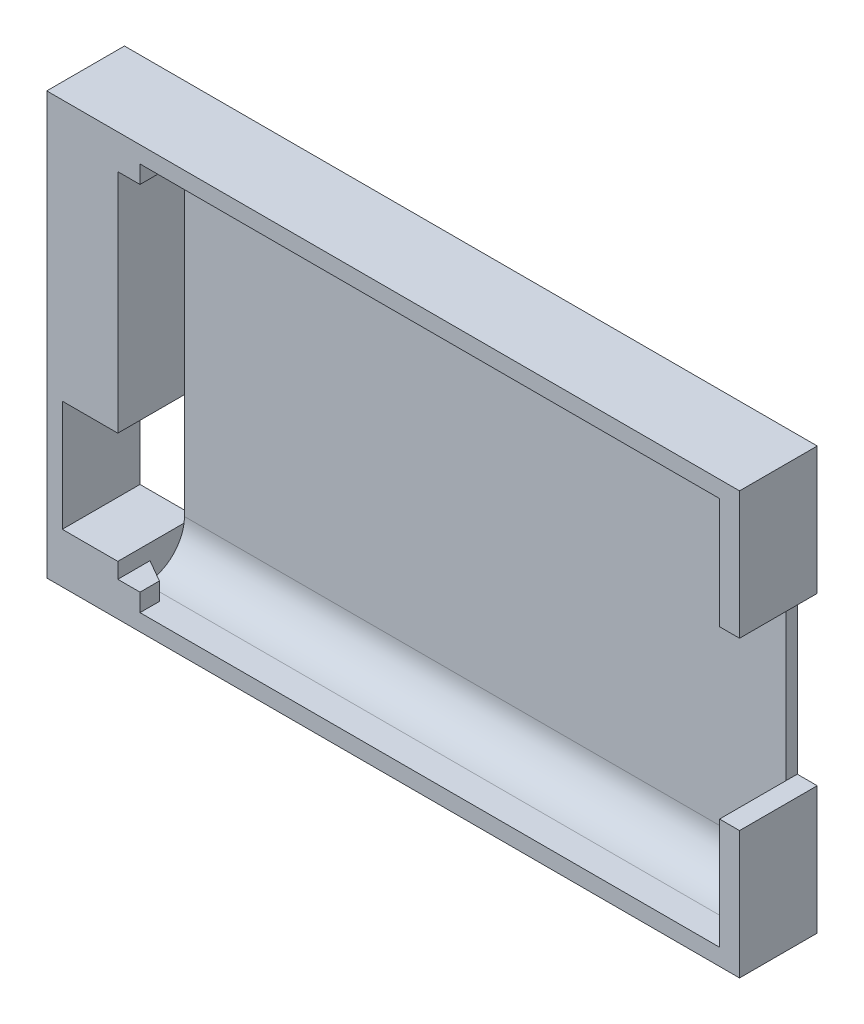
SolidWorks part; units mm, degrees
ref_plane "Front Plane" through (0, 0, 0) normal (0, 0, 1) x (1, 0, 0)
ref_plane "Top Plane" through (0, 0, 0) normal (0, 1, 0) x (1, 0, 0)
ref_plane "Right Plane" through (0, 0, 0) normal (1, 0, 0) x (0, 0, -1)
sketch "Sketch1" plane through (0, 0, 0) normal (0, 0, 1) x (1, 0, 0)
  line L1 (-26.5, 17) -> (26.5, 17)
  line L2 (-26.5, 17) -> (-26.5, -17)
  line L3 (-26.5, -17) -> (26.5, -17)
  line L4 (26.5, 17) -> (26.5, -17)
  line L5 (-26.5, 17) -> (26.5, -17) construction
  line L6 (-26.5, -17) -> (26.5, 17) construction
  point P0 (0, 0)
  dimension "D1" = 34
  dimension "D2" = 53
sketch "Sketch2" plane through (0, 0, 0) normal (0, 0, 1) x (1, 0, 0)
  line L1 (-33.5, 19) -> (28.9, 19)
  line L2 (-33.5, 19) -> (-33.5, -19)
  line L3 (-33.5, -19) -> (28.9, -19)
  line L4 (28.9, 19) -> (28.9, -19)
  line L6 (-26.5, 17) -> (-26.5, -17) construction
  line L7 (26.5, 17) -> (26.5, -17) construction
  line L8 (-26.5, -17) -> (-26.5, -19) construction
  line L9 (-26.5, 17) -> (-26.5, 19) construction
  line L10 (-26.5, 17) -> (26.5, 17) construction
  dimension "D1" = 7
  dimension "D2" = 2.4
  dimension "D3" = 2
extrude "Boss-Extrude1" add sketch "Sketch2" along normal blind 7
sketch "Sketch3" plane through (0, 0, 0) normal (1, 0, 0) x (0, 0, -1)
  line L0 (-7.5, 17) -> (-4.5, 17) construction
  line L1 (-1.5, 0) -> (-7.5, 0) construction
  line L2 (-7.5, -17) -> (-7.5, 17) construction
  line L3 (-1.5, -14) -> (-1.5, 14) construction
  line L4 (-7.5, -17) -> (-4.5, -17) construction
  line L5 (-8, 17.5) -> (-4.5, 17.5)
  line L6 (-1, -14) -> (-1, 14)
  line L7 (-8, -17.5) -> (-4.5, -17.5)
  line L8 (-8, -17.5) -> (-8, 17.5)
  arc A0 (-4.5, 17) -> (-1.5, 14) centre (-4.5, 14) cw construction
  arc A1 (-4.5, -17) -> (-1.5, -14) centre (-4.5, -14) ccw construction
  arc A2 (-4.5, 17.5) -> (-1, 14) centre (-4.5, 14) cw
  arc A3 (-4.5, -17.5) -> (-1, -14) centre (-4.5, -14) ccw
  point P6 (-12.641, 14.088)
  point P11 (-13.7836, 13.0913)
  dimension "D1" = 3
  dimension "D2" = 6
  dimension "D3" = 34
  dimension "D5" = 1
  dimension "D4" = 0.5
extrude "Cut-Extrude1" cut sketch "Sketch3" against normal mid plane 54.2
sketch "Sketch4" plane through (0, 0, 7) normal (0, 0, 1) x (1, 0, 0)
  line L1 (0, 0) -> (28, 0) construction
  line L2 (28.9, 7.5) -> (27.1, 7.5)
  line L3 (28.9, 7.5) -> (28.9, -7.5)
  line L4 (28.9, -7.5) -> (27.1, -7.5)
  line L7 (27.1, 7.5) -> (27.1, -7.5)
  line L8 (28.9, 7.5) -> (27.1, -7.5) construction
  line L9 (28.9, -7.5) -> (27.1, 7.5) construction
  line L10 (27.1, -14) -> (27.1, 14) construction
  line L11 (28.9, -19) -> (28.9, 19) construction
  line L12 (27.1, 17.5) -> (27.1, -17.5) construction
  point P0 (28, 0)
  point P12 (27.1, -5.5675)
  dimension "D1" = 15
extrude "ForFinger" cut sketch "Sketch4" against normal through all
sketch "Sketch8" plane through (0, 0, 1) normal (0, 0, 1) x (1, 0, 0)
  line L0 (-27.1, -17.5) -> (27.1, -17.5) construction
  line L1 (-27.1, 17.5) -> (-24.1, 17.5)
  line L2 (-27.1, 17.5) -> (-27.1, -17.5)
  line L3 (-27.1, -17.5) -> (-24.1, -17.5)
  line L4 (-24.1, 17.5) -> (-24.1, -17.5)
  dimension "D1" = 3
extrude "Cut-Extrude4" [suppressed] cut sketch "Sketch8" along normal through all
sketch "Sketch5" plane through (0, 17.5, 0) normal (0, -1, 0) x (1, 0, 0)
  line L0 (-27.1, 7) -> (-25.1, 7)
  line L1 (27.1, 7) -> (-27.1, 7) construction
  line L2 (-25.1, 7) -> (-25.1, 4.1)
  line L3 (-25.1, 4.1) -> (-27.1, 4.1)
  line L4 (-27.1, 4.1) -> (-27.1, 7)
  line L5 (-26.9, 4) -> (-24.9, 4) construction
  line L6 (-24.9, 4) -> (-24.9, 7) construction
  line L7 (-24.9, 7) -> (-20.5432, 7) construction
  line L8 (-26.9, 4) -> (-26.9, 1) construction
  line L9 (-26.9, 1) -> (-20.5432, 1) construction
  line L10 (-20.5432, 1) -> (-20.5432, 7) construction
  line L11 (-27.1, 1) -> (27.1, 1) construction
  line L12 (-27.1, 1) -> (-27.1, 4.5) construction
  point P9 (0, 0)
  point P14 (0, 0)
  point P15 (-20.5432, 1)
  point P18 (-24.4325, 2.1847)
  point P19 (-24.0137, 1)
  point P20 (-26.3689, 1)
  point P23 (-27.1, 3.7068)
  point P24 (-25.203, 5.2626)
  point P25 (-27.1, 4.2847)
  point P26 (-25.0697, 4.2847)
  dimension "D1" = 6
  dimension "D2" = 3
  dimension "D3" = 0.2
  dimension "D4" = 2
  dimension "D5" = 0.2
  dimension "D6" = 0.1
extrude "Boss-Extrude2" add sketch "Sketch5" along normal blind 1.6
chamfer "Chamfer1" distance 2 angle 30 1 edges at (-25.1, 16.6885, 4.1) first distance on face at (-26.1, 16.6885, 4.1)
mirror "Mirror1" about plane through (0, 0, 0) normal (0, 1, 0) of "Chamfer1", "Boss-Extrude2"
sketch "Sketch6" plane through (0, 0, 7) normal (0, 0, 1) x (1, 0, 0)
  line L1 (-32.1, -4.5) -> (-27.1, -4.5)
  line L2 (-32.1, -4.5) -> (-32.1, -14.5)
  line L3 (-32.1, -14.5) -> (-27.1, -14.5)
  line L4 (-27.1, -4.5) -> (-27.1, -14.5)
  line L5 (-27.1, -15.9) -> (-27.1, 15.9) construction
  line L7 (-26.5, -17) -> (26.5, -17) construction
  point P4 (-30.9225, -14.5)
  point P8 (-32.1, -9.5)
  dimension "D1" = 10
  dimension "D2" = 7.5
  dimension "D3" = 5
extrude "Cut-Extrude3" cut sketch "Sketch6" against normal through all
equation "\"D1@Cut-Extrude1\"=53/2+0.6"
equation "\"D2@Cut-Extrude1\"= 53/2+0.6"
